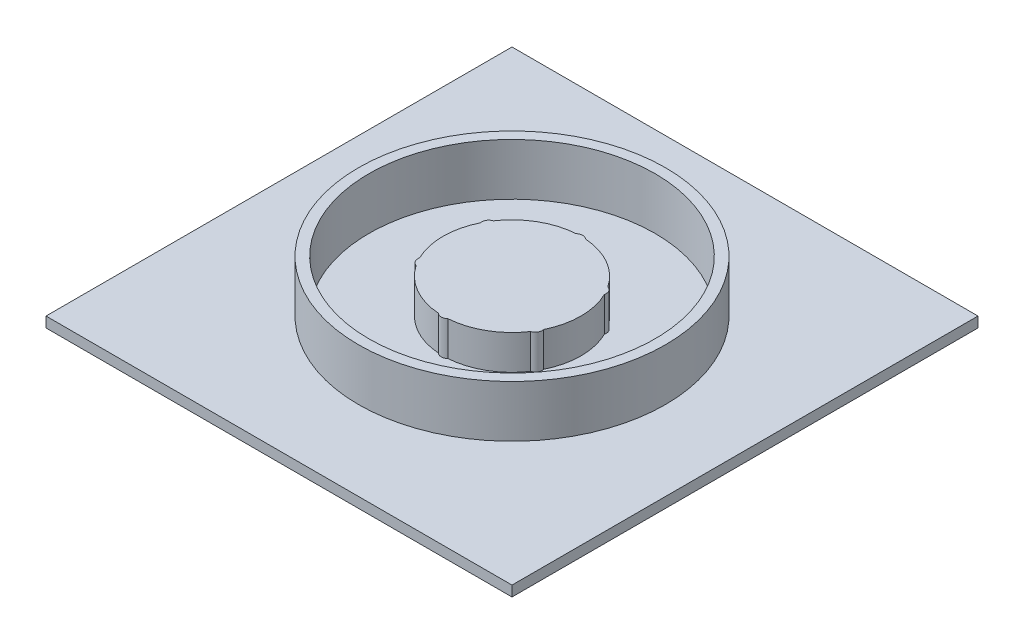
SolidWorks part; units mm, degrees
ref_plane "Front Plane" through (0, 0, 0) normal (0, 0, 1) x (1, 0, 0)
ref_plane "Top Plane" through (0, 0, 0) normal (0, 1, 0) x (1, 0, 0)
ref_plane "Right Plane" through (0, 0, 0) normal (1, 0, 0) x (0, 0, -1)
sketch "Sketch1" plane through (0, 0, 0) normal (0, 1, 0) x (1, 0, 0)
  line L1 (0, 0) -> (135, 0)
  line L2 (0, 0) -> (0, 135)
  line L3 (0, 135) -> (135, 135)
  line L4 (135, 0) -> (135, 135)
  dimension "D1" = 135
  dimension "D2" = 135
extrude "Boss-Extrude1" add sketch "Sketch1" along normal blind 3
sketch "Sketch2" plane through (0, 3, 0) normal (0, 1, 0) x (1, 0, 0)
  line L0 (0, 0) -> (135, 135) construction
  circle A0 centre (67.5, 67.5) radius 20
  arc A1 (66.1254, 87.4527) -> (68.8746, 87.4527) centre (67.5, 86) cw
  arc A2 (66.1254, 87.4527) -> (68.8746, 87.4527) centre (67.5, 67.5) cw
  arc A3 (84.0922, 78.6668) -> (85.4669, 76.2859) centre (83.5215, 76.75) cw
  arc A4 (84.0922, 78.6668) -> (85.4669, 76.2859) centre (67.5, 67.5) cw
  arc A5 (85.4669, 58.7141) -> (84.0922, 56.3332) centre (83.5215, 58.25) cw
  arc A6 (85.4669, 58.7141) -> (84.0922, 56.3332) centre (67.5, 67.5) cw
  arc A7 (68.8746, 47.5473) -> (66.1254, 47.5473) centre (67.5, 49) cw
  arc A8 (68.8746, 47.5473) -> (66.1254, 47.5473) centre (67.5, 67.5) cw
  arc A9 (50.9078, 56.3332) -> (49.5331, 58.7141) centre (51.4785, 58.25) cw
  arc A10 (50.9078, 56.3332) -> (49.5331, 58.7141) centre (67.5, 67.5) cw
  arc A11 (49.5331, 76.2859) -> (50.9078, 78.6668) centre (51.4785, 76.75) cw
  arc A12 (49.5331, 76.2859) -> (50.9078, 78.6668) centre (67.5, 67.5) cw
  point P28 (67.5, 67.5)
  dimension "D1" = 40
  dimension "D2" = 0.5
  dimension "D3" = 2
  dimension "D4" = 6
extrude "Boss-Extrude2" add sketch "Sketch2" along normal blind 10 contours A0 L0 | L0 A0 | A1 A0 | A7 A8 | A9 A10 | A5 A6 | A3 A4 | A11 A12 region at (61.4979, 3, -73.5021) region at (73.5021, 3, -61.4979) region at (67.5, 3, -87.693)
sketch "Sketch3" plane through (0, 3, 0) normal (0, 1, 0) x (1, 0, 0)
  circle A0 centre (67.5, 67.5) radius 44.45
  circle A1 centre (67.5, 67.5) radius 41.45
  dimension "D1" = 88.9
  dimension "D2" = 3
extrude "Boss-Extrude3" add sketch "Sketch3" along normal blind 15
